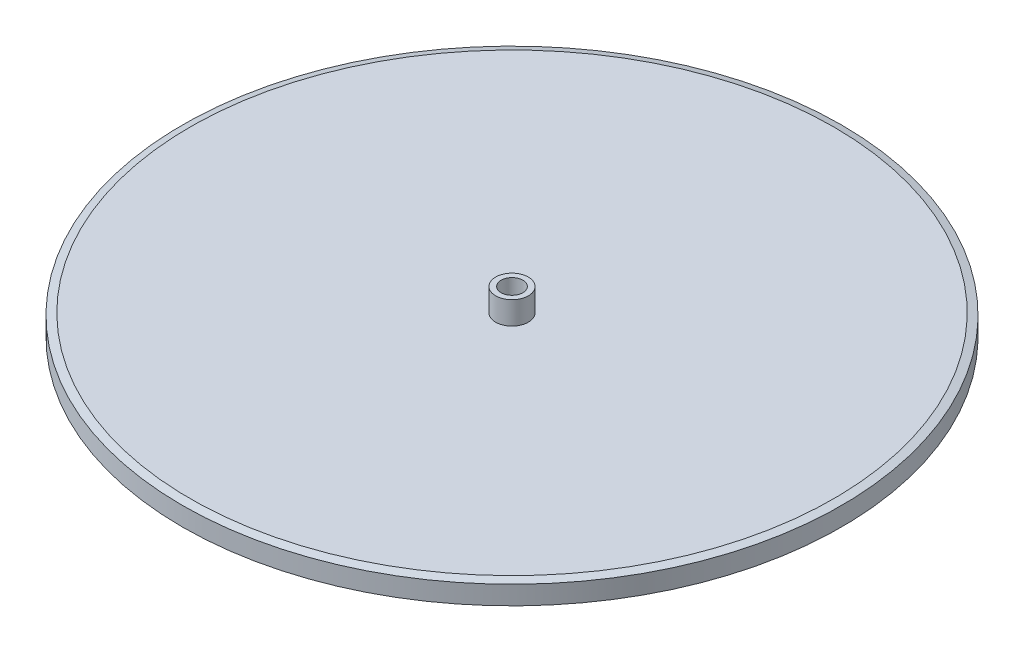
SolidWorks part; units mm, degrees
material "Сталь ШХ15 ГОСТ 801-78"
ref_plane "Plane1" through (0, 0, 0) normal (0, 0, 1) x (1, 0, 0)
ref_plane "Plane2" through (0, 0, 0) normal (0, 1, 0) x (1, 0, 0)
ref_plane "Plane3" through (0, 0, 0) normal (1, 0, 0) x (0, 0, -1)
sketch "Эскиз1" plane through (0, 0, 0) normal (0, 0, 1) x (1, 0, 0)
  line L0 (0, 0) -> (60.6, 0)
  line L1 (60.6, 0) -> (60.6, 4.2)
  line L2 (60.6, 4.2) -> (3, 4.2)
  line L3 (3, 4.2) -> (3, 8.4)
  line L4 (3, 8.4) -> (0, 8.4)
  line L5 (0, 8.4) -> (0, 0)
  dimension "D1" = 4.2
  dimension "30" = 60.6
  dimension "D3" = 3
  dimension "D4" = 4.2
ref_axis "Ось1" through (0, 8.4, 0) along (0, -1, 0)
revolve "Повернуть2" add sketch "Эскиз1" angle 360 about axis through (0, 8.4, 0) along (0, -1, 0)
chamfer "Фаска1" distance 1.41 angle 15 1 edges at (0, 4.2, 60.6) first distance on face at (0, 4.2, 3)
chamfer "Фаска2" distance 1.41 angle 15 1 edges at (0, 0, 60.6) first distance on face at (0, 0, 60.6)
sketch "Эскиз2" plane through (0, 0, 0) normal (0, -1, 0) x (-1, 0, 0)
  circle A0 centre (0, 0) radius 2
  dimension "D1" = 4
sketch "Эскиз3" plane through (0, 0, 0) normal (0, 0, 1) x (1, 0, 0)
  circle A0 centre (0, 5.828) radius 1
extrude "Вырез-Вытянуть3" cut sketch "Эскиз2" against normal through all both contours A0
